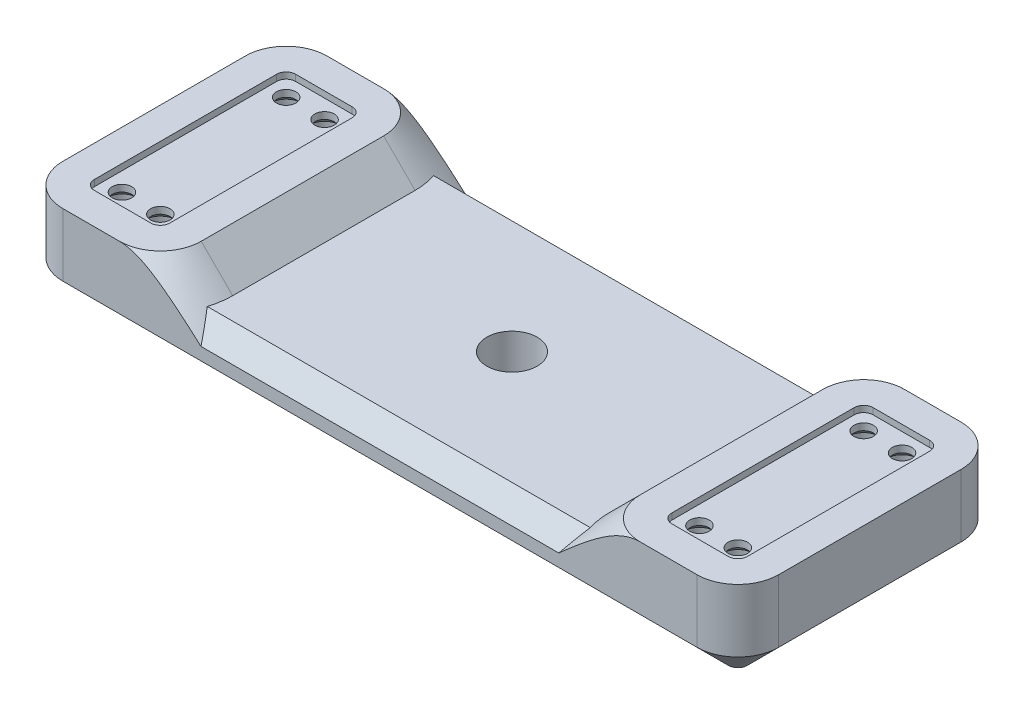
SolidWorks part; units mm, degrees
ref_plane "Front Plane" through (0, 0, 0) normal (0, 0, 1) x (1, 0, 0)
ref_plane "Top Plane" through (0, 0, 0) normal (0, 1, 0) x (1, 0, 0)
ref_plane "Right Plane" through (0, 0, 0) normal (1, 0, 0) x (0, 0, -1)
sketch "Sketch1" plane through (0, 0, 0) normal (0, 1, 0) x (1, 0, 0)
  line L0 (41.4, -16) -> (50.4, -16) construction
  line L1 (51.9, -14.5) -> (51.9, 14.5) construction
  line L2 (39.9, 14.5) -> (39.9, -14.5) construction
  line L3 (50.4, 16) -> (41.4, 16) construction
  line L4 (41.4, -16) -> (50.4, -16)
  line L5 (51.9, -14.5) -> (51.9, 14.5)
  line L6 (39.9, 14.5) -> (39.9, -14.5)
  line L7 (50.4, 16) -> (41.4, 16)
  line L8 (-50.4, -16) -> (-41.4, -16) construction
  line L9 (-51.9, 14.5) -> (-51.9, -14.5) construction
  line L10 (-39.9, -14.5) -> (-39.9, 14.5) construction
  line L11 (-41.4, 16) -> (-50.4, 16) construction
  line L12 (-50.4, -16) -> (-41.4, -16)
  line L13 (-51.9, 14.5) -> (-51.9, -14.5)
  line L14 (-39.9, -14.5) -> (-39.9, 14.5)
  line L15 (-41.4, 16) -> (-50.4, 16)
  line L16 (82.8, 19) -> (56.8, 19) construction
  line L17 (56.8, 15) -> (82.8, 15) construction
  line L18 (56.8, -19) -> (82.8, -19) construction
  line L19 (82.8, -15) -> (56.8, -15) construction
  line L20 (82.8, 19) -> (56.8, 19)
  line L21 (56.8, 15) -> (82.8, 15)
  line L22 (56.8, -19) -> (82.8, -19)
  line L23 (82.8, -15) -> (56.8, -15)
  line L24 (-82.8, 15) -> (-56.8, 15) construction
  line L25 (-56.8, 19) -> (-82.8, 19) construction
  line L26 (-56.8, -15) -> (-82.8, -15) construction
  line L27 (-82.8, -19) -> (-56.8, -19) construction
  line L28 (-82.8, 15) -> (-56.8, 15)
  line L29 (-56.8, 19) -> (-82.8, 19)
  line L30 (-56.8, -15) -> (-82.8, -15)
  line L31 (-82.8, -19) -> (-56.8, -19)
  line L32 (44.2143, 24.5366) -> (31.729, 24.5366) construction
  line L33 (44.2143, 24.5366) -> (31.729, 24.5366)
  line L34 (31.729, -24.5366) -> (44.2143, -24.5366) construction
  line L35 (31.729, -24.5366) -> (44.2143, -24.5366)
  line L36 (-44.2143, -24.5366) -> (-31.729, -24.5366) construction
  line L37 (-44.2143, -24.5366) -> (-31.729, -24.5366)
  line L38 (-31.729, 24.5366) -> (-44.2143, 24.5366) construction
  line L39 (-31.729, 24.5366) -> (-44.2143, 24.5366)
  arc A0 (50.4, -16) -> (51.9, -14.5) centre (50.4, -14.5) ccw construction
  arc A1 (51.9, 14.5) -> (50.4, 16) centre (50.4, 14.5) ccw construction
  arc A2 (39.9, -14.5) -> (41.4, -16) centre (41.4, -14.5) ccw construction
  arc A3 (41.4, 16) -> (39.9, 14.5) centre (41.4, 14.5) ccw construction
  arc A4 (50.4, -16) -> (51.9, -14.5) centre (50.4, -14.5) ccw
  arc A5 (51.9, 14.5) -> (50.4, 16) centre (50.4, 14.5) ccw
  arc A6 (39.9, -14.5) -> (41.4, -16) centre (41.4, -14.5) ccw
  arc A7 (41.4, 16) -> (39.9, 14.5) centre (41.4, 14.5) ccw
  arc A8 (-51.9, -14.5) -> (-50.4, -16) centre (-50.4, -14.5) ccw construction
  arc A9 (-41.4, -16) -> (-39.9, -14.5) centre (-41.4, -14.5) ccw construction
  arc A10 (-50.4, 16) -> (-51.9, 14.5) centre (-50.4, 14.5) ccw construction
  arc A11 (-39.9, 14.5) -> (-41.4, 16) centre (-41.4, 14.5) ccw construction
  arc A12 (-51.9, -14.5) -> (-50.4, -16) centre (-50.4, -14.5) ccw
  arc A13 (-41.4, -16) -> (-39.9, -14.5) centre (-41.4, -14.5) ccw
  arc A14 (-50.4, 16) -> (-51.9, 14.5) centre (-50.4, 14.5) ccw
  arc A15 (-39.9, 14.5) -> (-41.4, 16) centre (-41.4, 14.5) ccw
  arc A16 (82.8, 15) -> (82.8, 19) centre (82.8, 17) ccw construction
  arc A17 (56.8, 19) -> (56.8, 15) centre (56.8, 17) ccw construction
  arc A18 (82.8, -19) -> (82.8, -15) centre (82.8, -17) ccw construction
  arc A19 (56.8, -15) -> (56.8, -19) centre (56.8, -17) ccw construction
  arc A20 (82.8, 15) -> (82.8, 19) centre (82.8, 17) ccw
  arc A21 (56.8, 19) -> (56.8, 15) centre (56.8, 17) ccw
  arc A22 (82.8, -19) -> (82.8, -15) centre (82.8, -17) ccw
  arc A23 (56.8, -15) -> (56.8, -19) centre (56.8, -17) ccw
  arc A24 (-56.8, 15) -> (-56.8, 19) centre (-56.8, 17) ccw construction
  arc A25 (-82.8, 19) -> (-82.8, 15) centre (-82.8, 17) ccw construction
  arc A26 (-56.8, -19) -> (-56.8, -15) centre (-56.8, -17) ccw construction
  arc A27 (-82.8, -15) -> (-82.8, -19) centre (-82.8, -17) ccw construction
  arc A28 (-56.8, 15) -> (-56.8, 19) centre (-56.8, 17) ccw
  arc A29 (-82.8, 19) -> (-82.8, 15) centre (-82.8, 17) ccw
  arc A30 (-56.8, -19) -> (-56.8, -15) centre (-56.8, -17) ccw
  arc A31 (-82.8, -15) -> (-82.8, -19) centre (-82.8, -17) ccw
sketch "Sketch2" plane through (0, 0, 0) normal (0, 1, 0) x (1, 0, 0)
  line L0 (39.9, 14.5) -> (39.9, -14.5) construction
  line L1 (50.4, 16) -> (41.4, 16) construction
  line L2 (-41.4, 16) -> (-50.4, 16) construction
  line L3 (-51.9, 14.5) -> (-51.9, -14.5) construction
  line L4 (-50.4, -16) -> (-41.4, -16) construction
  line L5 (-39.9, -14.5) -> (-39.9, 14.5) construction
  line L6 (41.4, -16) -> (50.4, -16) construction
  line L7 (51.9, -14.5) -> (51.9, 14.5) construction
  line L8 (-41.4, 16) -> (-50.4, 16) construction
  line L9 (-51.9, 14.5) -> (-51.9, -14.5) construction
  line L10 (-50.4, -16) -> (-41.4, -16) construction
  line L11 (-39.9, -14.5) -> (-39.9, 14.5) construction
  line L12 (41.4, -16) -> (50.4, -16) construction
  line L13 (39.9, 14.5) -> (39.9, -14.5) construction
  line L14 (51.9, -14.5) -> (51.9, 14.5) construction
  line L15 (50.4, 16) -> (41.4, 16) construction
  line L16 (-41.4, 21) -> (-50.4, 21)
  line L17 (-56.9, 14.5) -> (-56.9, -14.5)
  line L18 (-50.4, -21) -> (-41.4, -21)
  line L19 (-34.9, -14.5) -> (-34.9, 14.5)
  line L20 (41.4, -21) -> (50.4, -21)
  line L21 (56.9, -14.5) -> (56.9, 14.5)
  line L22 (50.4, 21) -> (41.4, 21)
  line L23 (34.9, 14.5) -> (34.9, -14.5)
  arc A0 (41.4, 16) -> (39.9, 14.5) centre (41.4, 14.5) ccw construction
  arc A1 (-39.9, 14.5) -> (-41.4, 16) centre (-41.4, 14.5) ccw construction
  arc A2 (-50.4, 16) -> (-51.9, 14.5) centre (-50.4, 14.5) ccw construction
  arc A3 (-51.9, -14.5) -> (-50.4, -16) centre (-50.4, -14.5) ccw construction
  arc A4 (-41.4, -16) -> (-39.9, -14.5) centre (-41.4, -14.5) ccw construction
  arc A5 (50.4, -16) -> (51.9, -14.5) centre (50.4, -14.5) ccw construction
  arc A6 (39.9, -14.5) -> (41.4, -16) centre (41.4, -14.5) ccw construction
  arc A7 (51.9, 14.5) -> (50.4, 16) centre (50.4, 14.5) ccw construction
  arc A8 (-39.9, 14.5) -> (-41.4, 16) centre (-41.4, 14.5) ccw construction
  arc A9 (-50.4, 16) -> (-51.9, 14.5) centre (-50.4, 14.5) ccw construction
  arc A10 (-51.9, -14.5) -> (-50.4, -16) centre (-50.4, -14.5) ccw construction
  arc A11 (-41.4, -16) -> (-39.9, -14.5) centre (-41.4, -14.5) ccw construction
  arc A12 (50.4, -16) -> (51.9, -14.5) centre (50.4, -14.5) ccw construction
  arc A13 (39.9, -14.5) -> (41.4, -16) centre (41.4, -14.5) ccw construction
  arc A14 (51.9, 14.5) -> (50.4, 16) centre (50.4, 14.5) ccw construction
  arc A15 (41.4, 16) -> (39.9, 14.5) centre (41.4, 14.5) ccw construction
  arc A16 (-50.4, 21) -> (-56.9, 14.5) centre (-50.4, 14.5) ccw
  arc A17 (-56.9, -14.5) -> (-50.4, -21) centre (-50.4, -14.5) ccw
  arc A18 (-41.4, -21) -> (-34.9, -14.5) centre (-41.4, -14.5) ccw
  arc A19 (-34.9, 14.5) -> (-41.4, 21) centre (-41.4, 14.5) ccw
  arc A20 (50.4, -21) -> (56.9, -14.5) centre (50.4, -14.5) ccw
  arc A21 (56.9, 14.5) -> (50.4, 21) centre (50.4, 14.5) ccw
  arc A22 (41.4, 21) -> (34.9, 14.5) centre (41.4, 14.5) ccw
  arc A23 (34.9, -14.5) -> (41.4, -21) centre (41.4, -14.5) ccw
  point P48 (-45.9, 0)
  point P49 (45.9, 0)
  point P51 (-51.9, 0)
  point P53 (-45.9, 16)
  point P55 (45.9, 16)
  point P57 (51.9, 0)
  dimension "D1" = 5
  dimension "D2" = 5
extrude "Boss-Extrude1" add sketch "Sketch2" against normal blind 15
sketch "Sketch4" plane through (0, -15, 0) normal (0, -1, 0) x (1, 0, 0)
  line L4 (34.9, 14.5) -> (34.9, -14.5)
  line L5 (41.4, -21) -> (50.4, -21)
  line L6 (56.9, -14.5) -> (56.9, 14.5)
  line L7 (50.4, 21) -> (41.4, 21)
  line L9 (-50.4, -21) -> (50.4, -21)
  line L10 (56.9, -14.5) -> (56.9, 14.5)
  line L11 (50.4, 21) -> (-50.4, 21)
  line L12 (-34.9, -14.5) -> (-34.9, 14.5)
  line L13 (-41.4, 21) -> (-50.4, 21)
  line L14 (-56.9, 14.5) -> (-56.9, -14.5)
  line L15 (-50.4, -21) -> (-41.4, -21)
  line L18 (-56.9, 14.5) -> (-56.9, -14.5)
  arc A4 (41.4, 21) -> (34.9, 14.5) centre (41.4, 14.5) ccw
  arc A5 (34.9, -14.5) -> (41.4, -21) centre (41.4, -14.5) ccw
  arc A6 (50.4, -21) -> (56.9, -14.5) centre (50.4, -14.5) ccw
  arc A7 (56.9, 14.5) -> (50.4, 21) centre (50.4, 14.5) ccw
  arc A10 (50.4, -21) -> (56.9, -14.5) centre (50.4, -14.5) ccw
  arc A11 (56.9, 14.5) -> (50.4, 21) centre (50.4, 14.5) ccw
  arc A12 (-41.4, -21) -> (-34.9, -14.5) centre (-41.4, -14.5) ccw
  arc A13 (-34.9, 14.5) -> (-41.4, 21) centre (-41.4, 14.5) ccw
  arc A14 (-50.4, 21) -> (-56.9, 14.5) centre (-50.4, 14.5) ccw
  arc A15 (-56.9, -14.5) -> (-50.4, -21) centre (-50.4, -14.5) ccw
  arc A18 (-50.4, 21) -> (-56.9, 14.5) centre (-50.4, 14.5) ccw
  arc A19 (-56.9, -14.5) -> (-50.4, -21) centre (-50.4, -14.5) ccw
  dimension "D1" = 0
  dimension "D2" = 0
extrude "Boss-Extrude2" add sketch "Sketch4" against normal blind 10
chamfer "Chamfer1" distance 5 14 edges at (0, -15, -21) (-54.9962, -15, -19.0962) (54.9962, -15, -19.0962) (-56.9, -15, 0) (56.9, -15, 0) (-54.9962, -15, 19.0962) (54.9962, -15, 19.0962) (0, -15, 21) (36.8038, -5, 19.0962) (36.8038, -5, -19.0962) (34.9, -5, 0) (-36.8038, -5, 19.0962) (-36.8038, -5, -19.0962) (-34.9, -5, 0)
sketch "Sketch5" plane through (0, 0, 0) normal (0, 1, 0) x (1, 0, 0)
  line L0 (41.4, -16) -> (50.4, -16) construction
  line L1 (51.9, -14.5) -> (51.9, 14.5) construction
  line L2 (39.9, 14.5) -> (39.9, -14.5) construction
  line L3 (50.4, 16) -> (41.4, 16) construction
  line L4 (-50.4, -16) -> (-41.4, -16) construction
  line L5 (-39.9, -14.5) -> (-39.9, 14.5) construction
  line L6 (-51.9, 14.5) -> (-51.9, -14.5) construction
  line L7 (-41.4, 16) -> (-50.4, 16) construction
  line L8 (41.4, -16) -> (50.4, -16)
  line L9 (51.9, -14.5) -> (51.9, 14.5)
  line L10 (39.9, 14.5) -> (39.9, -14.5)
  line L11 (50.4, 16) -> (41.4, 16)
  line L12 (-50.4, -16) -> (-41.4, -16)
  line L13 (-39.9, -14.5) -> (-39.9, 14.5)
  line L14 (-51.9, 14.5) -> (-51.9, -14.5)
  line L15 (-41.4, 16) -> (-50.4, 16)
  arc A0 (50.4, -16) -> (51.9, -14.5) centre (50.4, -14.5) ccw construction
  arc A1 (39.9, -14.5) -> (41.4, -16) centre (41.4, -14.5) ccw construction
  arc A2 (51.9, 14.5) -> (50.4, 16) centre (50.4, 14.5) ccw construction
  arc A3 (41.4, 16) -> (39.9, 14.5) centre (41.4, 14.5) ccw construction
  arc A4 (-51.9, -14.5) -> (-50.4, -16) centre (-50.4, -14.5) ccw construction
  arc A5 (-41.4, -16) -> (-39.9, -14.5) centre (-41.4, -14.5) ccw construction
  arc A6 (-39.9, 14.5) -> (-41.4, 16) centre (-41.4, 14.5) ccw construction
  arc A7 (-50.4, 16) -> (-51.9, 14.5) centre (-50.4, 14.5) ccw construction
  arc A8 (50.4, -16) -> (51.9, -14.5) centre (50.4, -14.5) ccw
  arc A9 (39.9, -14.5) -> (41.4, -16) centre (41.4, -14.5) ccw
  arc A10 (51.9, 14.5) -> (50.4, 16) centre (50.4, 14.5) ccw
  arc A11 (41.4, 16) -> (39.9, 14.5) centre (41.4, 14.5) ccw
  arc A12 (-51.9, -14.5) -> (-50.4, -16) centre (-50.4, -14.5) ccw
  arc A13 (-41.4, -16) -> (-39.9, -14.5) centre (-41.4, -14.5) ccw
  arc A14 (-39.9, 14.5) -> (-41.4, 16) centre (-41.4, 14.5) ccw
  arc A15 (-50.4, 16) -> (-51.9, 14.5) centre (-50.4, 14.5) ccw
extrude "Cut-Extrude1" cut sketch "Sketch5" against normal blind 1
ref_plane "Plane1" through (0, -2, 0) normal (0, 1, 0) x (1, 0, 0)
sketch "Sketch6" plane through (0, -2, 0) normal (0, 1, 0) x (1, 0, 0)
  line L0 (50.4, 15.5) -> (41.4, 15.5) construction
  line L1 (40.4, 14.5) -> (40.4, -14.5) construction
  line L2 (41.4, -15.5) -> (50.4, -15.5) construction
  line L3 (51.4, -14.5) -> (51.4, 14.5) construction
  line L4 (50.4, 16) -> (41.4, 16)
  line L5 (51.9, -14.5) -> (51.9, 14.5)
  line L6 (41.4, -16) -> (50.4, -16)
  line L7 (39.9, 14.5) -> (39.9, -14.5)
  line L8 (50.4, 16) -> (41.4, 16) construction
  line L9 (51.9, -14.5) -> (51.9, 14.5) construction
  line L10 (41.4, -16) -> (50.4, -16) construction
  line L11 (39.9, 14.5) -> (39.9, -14.5) construction
  line L12 (-41.4, 16) -> (-50.4, 16)
  line L13 (-39.9, -14.5) -> (-39.9, 14.5)
  line L14 (-50.4, -16) -> (-41.4, -16)
  line L15 (-51.9, 14.5) -> (-51.9, -14.5)
  line L16 (-41.4, 16) -> (-50.4, 16) construction
  line L17 (-39.9, -14.5) -> (-39.9, 14.5) construction
  line L18 (-50.4, -16) -> (-41.4, -16) construction
  line L19 (-51.9, 14.5) -> (-51.9, -14.5) construction
  line L20 (-41.4, 15.5) -> (-50.4, 15.5) construction
  line L21 (-51.4, 14.5) -> (-51.4, -14.5) construction
  line L22 (-50.4, -15.5) -> (-41.4, -15.5) construction
  line L23 (-40.4, -14.5) -> (-40.4, 14.5) construction
  arc A0 (41.4, 15.5) -> (40.4, 14.5) centre (41.4, 14.5) ccw construction
  arc A1 (40.4, -14.5) -> (41.4, -15.5) centre (41.4, -14.5) ccw construction
  arc A2 (50.4, -15.5) -> (51.4, -14.5) centre (50.4, -14.5) ccw construction
  arc A3 (51.4, 14.5) -> (50.4, 15.5) centre (50.4, 14.5) ccw construction
  arc A4 (51.9, 14.5) -> (50.4, 16) centre (50.4, 14.5) ccw
  arc A5 (50.4, -16) -> (51.9, -14.5) centre (50.4, -14.5) ccw
  arc A6 (39.9, -14.5) -> (41.4, -16) centre (41.4, -14.5) ccw
  arc A7 (41.4, 16) -> (39.9, 14.5) centre (41.4, 14.5) ccw
  arc A8 (51.9, 14.5) -> (50.4, 16) centre (50.4, 14.5) ccw construction
  arc A9 (50.4, -16) -> (51.9, -14.5) centre (50.4, -14.5) ccw construction
  arc A10 (39.9, -14.5) -> (41.4, -16) centre (41.4, -14.5) ccw construction
  arc A11 (41.4, 16) -> (39.9, 14.5) centre (41.4, 14.5) ccw construction
  arc A12 (-50.4, 16) -> (-51.9, 14.5) centre (-50.4, 14.5) ccw
  arc A13 (-39.9, 14.5) -> (-41.4, 16) centre (-41.4, 14.5) ccw
  arc A14 (-41.4, -16) -> (-39.9, -14.5) centre (-41.4, -14.5) ccw
  arc A15 (-51.9, -14.5) -> (-50.4, -16) centre (-50.4, -14.5) ccw
  arc A16 (-50.4, 16) -> (-51.9, 14.5) centre (-50.4, 14.5) ccw construction
  arc A17 (-39.9, 14.5) -> (-41.4, 16) centre (-41.4, 14.5) ccw construction
  arc A18 (-41.4, -16) -> (-39.9, -14.5) centre (-41.4, -14.5) ccw construction
  arc A19 (-51.9, -14.5) -> (-50.4, -16) centre (-50.4, -14.5) ccw construction
  arc A20 (-50.4, 15.5) -> (-51.4, 14.5) centre (-50.4, 14.5) ccw construction
  arc A21 (-51.4, -14.5) -> (-50.4, -15.5) centre (-50.4, -14.5) ccw construction
  arc A22 (-41.4, -15.5) -> (-40.4, -14.5) centre (-41.4, -14.5) ccw construction
  arc A23 (-40.4, 14.5) -> (-41.4, 15.5) centre (-41.4, 14.5) ccw construction
  circle A24 centre (-48.95, 13.05) radius 2.45
  circle A25 centre (-42.85, 13.05) radius 2.45
  circle A26 centre (-48.95, -13.05) radius 2.45
  circle A27 centre (-42.85, -13.05) radius 2.45
  circle A28 centre (42.85, 13.05) radius 2.45
  circle A29 centre (48.95, 13.05) radius 2.45
  circle A30 centre (42.85, -13.05) radius 2.45
  circle A31 centre (48.95, -13.05) radius 2.45
  dimension "D4" = 4.9
  dimension "D1" = 0
  dimension "D2" = 0
  dimension "D3" = 0.5
extrude "Cut-Extrude2" cut sketch "Sketch6" against normal through all
sketch "Sketch7" plane through (0, -2, 0) normal (0, -1, 0) x (1, 0, 0)
  circle A0 centre (-48.95, 13.05) radius 1.55
  circle A1 centre (-42.85, 13.05) radius 1.55
  circle A2 centre (-42.85, -13.05) radius 1.55
  circle A3 centre (-48.95, -13.05) radius 1.55
  circle A4 centre (48.95, 13.05) radius 1.55
  circle A5 centre (42.85, 13.05) radius 1.55
  circle A6 centre (42.85, -13.05) radius 1.55
  circle A7 centre (48.95, -13.05) radius 1.55
  dimension "D1" = 3.1
extrude "Cut-Extrude3" cut sketch "Sketch7" against normal up to next
chamfer "Chamfer3" distance 0.975 angle 45 8 edges at (-42.85, -2, 15.5) (-48.95, -2, 15.5) (-42.85, -2, -10.6) (-48.95, -2, -10.6) (48.95, -2, -10.6) (42.85, -2, -10.6) (48.95, -2, 15.5) (42.85, -2, 15.5)
chamfer "Chamfer4" distance 3 angle 45 2 edges at (0, -5, -21) (0, -5, 21)
ref_plane "Plane2" through (0, -14, 0) normal (0, -1, 0) x (-1, 0, 0)
sketch "Sketch8" plane through (0, -14, 0) normal (0, -1, 0) x (-1, 0, 0)
  circle A0 centre (0, 0) radius 4
  dimension "D1" = 8
extrude "Cut-Extrude4" cut sketch "Sketch8" against normal up to next
sketch "Sketch9" plane through (0, -14, 0) normal (0, 1, 0) x (1, 0, 0)
  circle A0 centre (0, 0) radius 3.05
  dimension "D1" = 6.1
extrude "Cut-Extrude5" cut sketch "Sketch9" against normal up to next
ref_plane "Plane3" through (45.9, 0, 0) normal (1, 0, 0) x (0, 0, -1)
